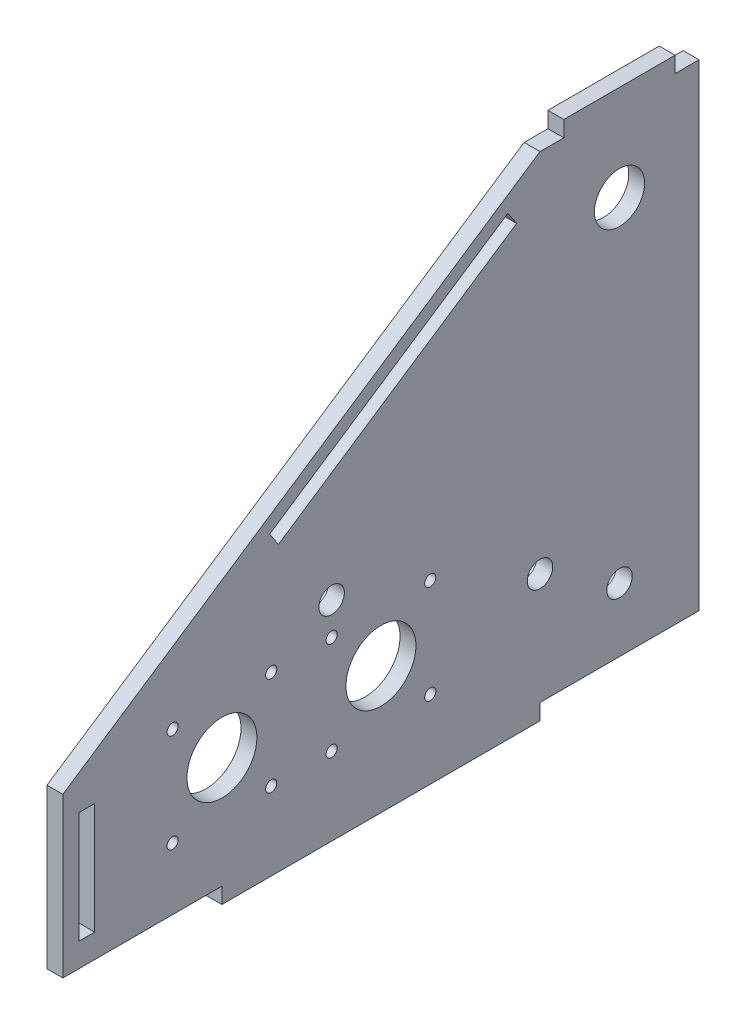
SolidWorks part; units mm, degrees
ref_plane "Alzado" through (0, 0, 0) normal (0, 0, 1) x (1, 0, 0)
ref_plane "Planta" through (0, 0, 0) normal (0, 1, 0) x (1, 0, 0)
ref_plane "Vista lateral" through (0, 0, 0) normal (1, 0, 0) x (0, 0, -1)
sketch "Croquis1" plane through (0, 0, 0) normal (1, 0, 0) x (0, 0, -1)
  line L0 (150, 150) -> (0, 50)
  line L1 (0, 0) -> (50, 0)
  line L2 (0, 0) -> (0, 50)
  line L3 (150, 150) -> (157.5, 150)
  line L4 (200, 0) -> (200, 150)
  line L5 (200, 75) -> (37.5, 75) construction
  line L6 (175, 155) -> (175, 0) construction
  line L7 (100, 116.6667) -> (100, -5) construction
  line L8 (84.5, 106.3333) -> (84.5, -5) construction
  line L9 (50, 0) -> (50, -5)
  line L10 (50, -5) -> (150, -5)
  line L11 (150, 0) -> (150, -5)
  line L12 (154, 35) -> (0, 35) construction
  line L13 (192.5, 150) -> (200, 150)
  line L14 (150, 0) -> (200, 0)
  line L15 (65, 88.3333) -> (139.8845, 138.2564)
  line L16 (157.5, 150) -> (157.5, 155)
  line L17 (157.5, 155) -> (192.5, 155)
  line L18 (192.5, 150) -> (192.5, 155)
  line L19 (139.8845, 138.2564) -> (142.658, 134.0961)
  line L20 (142.658, 134.0961) -> (67.7735, 84.1731)
  line L21 (67.7735, 84.1731) -> (65, 88.3333)
  line L22 (5, 53.3333) -> (5, 0) construction
  line L23 (65, 88.3333) -> (5, 48.3333) construction
  line L25 (5, 42.5) -> (10, 42.5)
  line L26 (5, 42.5) -> (5, 7.5)
  line L27 (5, 7.5) -> (10, 7.5)
  line L28 (10, 42.5) -> (10, 7.5)
  circle A0 centre (175, 125) radius 7.9
  circle A1 centre (175, 20) radius 4
  circle A2 centre (150, 35) radius 4
  circle A5 centre (100, 35) radius 11
  circle A6 centre (84.5, 60.6856) radius 4
  circle A9 centre (84.5, 50.5) radius 1.75
  circle A10 centre (115.5, 50.5) radius 1.75
  circle A11 centre (115.5, 19.5) radius 1.75
  circle A12 centre (84.5, 19.5) radius 1.75
  circle A13 centre (50, 35) radius 11
  circle A16 centre (34.5, 50.5) radius 1.75
  circle A17 centre (65.5, 50.5) radius 1.75
  circle A18 centre (65.5, 19.5) radius 1.75
  circle A19 centre (34.5, 19.5) radius 1.75
  point P74 (0, 0)
  dimension "D6" = 15.8
  dimension "D10" = 8
  dimension "D12" = 8
  dimension "D15" = 22
  dimension "D20" = 40
  dimension "D22" = 2
  dimension "D27" = 3.5
  dimension "D21" = 8
  dimension "D1" = 150
  dimension "D2" = 200
  dimension "D3" = 50
  dimension "D4" = 50
  dimension "D5" = 50
  dimension "D7" = 100
  dimension "D8" = 50
  dimension "D9" = 5
  dimension "D11" = 20
  dimension "D13" = 25
  dimension "D14" = 15
  dimension "D19" = 30
  dimension "D26" = 15.5
  dimension "D28" = 15.5
  dimension "D31" = 35
  dimension "D32" = 5
  dimension "D33" = 90
  dimension "D34" = 15
  dimension "D35" = 5
  dimension "D36" = 5
  dimension "D37" = 35
  dimension "D38" = 7.5
  dimension "D39" = 35
  dimension "D40" = 7.5
  dimension "D41" = 5
  dimension "D29" = 2
  dimension "D30" = 2
extrude "Saliente-Extruir1" add sketch "Croquis1" along normal blind 5
